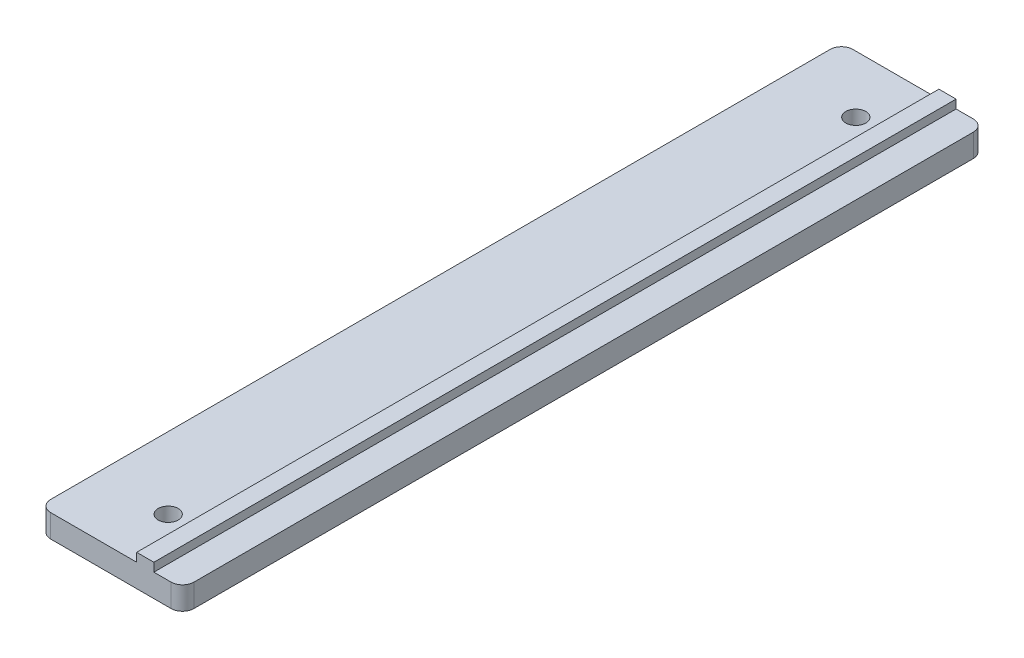
SolidWorks part; units mm, degrees
ref_plane "前视基准面" through (0, 0, 0) normal (0, 0, 1) x (1, 0, 0)
ref_plane "上视基准面" through (0, 0, 0) normal (0, 1, 0) x (1, 0, 0)
ref_plane "右视基准面" through (0, 0, 0) normal (1, 0, 0) x (0, 0, -1)
sketch "草图1" plane through (0, 0, 0) normal (0, 1, 0) x (1, 0, 0)
  line L1 (-12.5, -70) -> (12.5, -70)
  line L2 (-12.5, -70) -> (-12.5, 70)
  line L3 (-12.5, 70) -> (12.5, 70)
  line L4 (12.5, -70) -> (12.5, 70)
  line L5 (-12.5, -70) -> (12.5, 70) construction
  line L6 (-12.5, 70) -> (12.5, -70) construction
  point P0 (0, 0)
  dimension "D1" = 25
  dimension "D2" = 140
extrude "凸台-拉伸1" add sketch "草图1" along normal blind 4
sketch "草图2" plane through (0, 4, 0) normal (0, 1, 0) x (1, 0, 0)
  line L0 (0, 70) -> (0, -70) construction
  line L1 (12.5, 70) -> (-12.5, 70) construction
  line L2 (-12.5, -70) -> (12.5, -70) construction
  line L3 (0, 0) -> (12.5, 0) construction
  line L4 (12.5, -70) -> (12.5, 70) construction
  circle A0 centre (0, 0) radius 1.6 construction
  circle A1 centre (0, 20) radius 1.6 construction
  circle A2 centre (0, 40) radius 1.6 construction
  circle A3 centre (0, -40) radius 1.6 construction
  circle A4 centre (0, -20) radius 1.6 construction
  circle A5 centre (0, 10) radius 1.6
  circle A6 centre (0, 30) radius 1.6
  circle A7 centre (0, 50) radius 1.6
  circle A8 centre (0, -10) radius 1.6
  circle A9 centre (0, -30) radius 1.6
  circle A10 centre (0, -50) radius 1.6
  dimension "D1" = 3.2
  dimension "D4" = 3.2
  dimension "D3" = 20
  dimension "D5" = 10
  dimension "D7" = 20
  dimension "D2" = 3
  dimension "D6" = 3
sketch "草图3" plane through (0, 4, 0) normal (0, 1, 0) x (1, 0, 0)
  line L0 (-12.5, 0) -> (12.5, 0) construction
  line L1 (-12.5, 70) -> (-12.5, -70) construction
  line L2 (12.5, -70) -> (12.5, 70) construction
  line L3 (-12.5, 30) -> (12.5, 30) construction
  line L4 (0, 0) -> (0, 30) construction
  line B0 (-8, 37.5) -> (-8, 22.5) construction
  line B1 (-8, 37.5) -> (8, 37.5) construction
  line B2 (8, 37.5) -> (8, 22.5) construction
  line B3 (-8, 22.5) -> (8, 22.5) construction
  line B4 (0, 37.5) -> (0, 30) construction
  circle B5 centre (8, 37.5) radius 1.6
  circle B6 centre (8, 22.5) radius 1.6
  circle B7 centre (-8, 37.5) radius 1.6
  circle B8 centre (-8, 22.5) radius 1.6
  line B9 (-8, -37.5) -> (-8, -22.5) construction
  line B10 (-8, -37.5) -> (8, -37.5) construction
  line B11 (8, -37.5) -> (8, -22.5) construction
  line B12 (-8, -22.5) -> (8, -22.5) construction
  circle B13 centre (8, -37.5) radius 1.6
  circle B14 centre (8, -22.5) radius 1.6
  circle B15 centre (-8, -37.5) radius 1.6
  circle B16 centre (-8, -22.5) radius 1.6
  dimension "D1" = 30
sketch_block_instance "MGN9H导轨滑块孔-1"
sketch_block "MGN9H导轨滑块孔" parameters "D3"=3.2, "D1"=15, "D2"=16
sketch_block_instance "MGN9H导轨滑块孔-3"
fillet "圆角1" radius 2 4 edges at (12.5, 2, -70) (-12.5, 2, -70) (-12.5, 2, 70) (12.5, 2, 70)
sketch "草图4" plane through (0, 4, 0) normal (0, 1, 0) x (1, 0, 0)
  line L0 (-12.5, 0) -> (0, 0) construction
  line L1 (-12.5, 68) -> (-12.5, -68) construction
  line L2 (0, 70) -> (0, -70) construction
  circle A0 centre (0, 60) radius 1.75
  circle A1 centre (0, -60) radius 1.75
  dimension "D1" = 3.5
  dimension "D2" = 120
extrude "切除-拉伸1" cut sketch "草图4" against normal blind 10
sketch "草图6" plane through (0, 4, 0) normal (0, 1, 0) x (1, 0, 0)
  line L0 (10.5, 70) -> (-10.5, 70) construction
  line L1 (4.5, 70) -> (7.5, 70)
  line L2 (4.5, 70) -> (4.5, -70)
  line L3 (4.5, -70) -> (7.5, -70)
  line L4 (7.5, 70) -> (7.5, -70)
  line L5 (-10.5, -70) -> (10.5, -70) construction
  line L6 (12.5, -68) -> (12.5, 68) construction
  dimension "D1" = 8
  dimension "D2" = 3
extrude "凸台-拉伸3" add sketch "草图6" along normal blind 1.5
